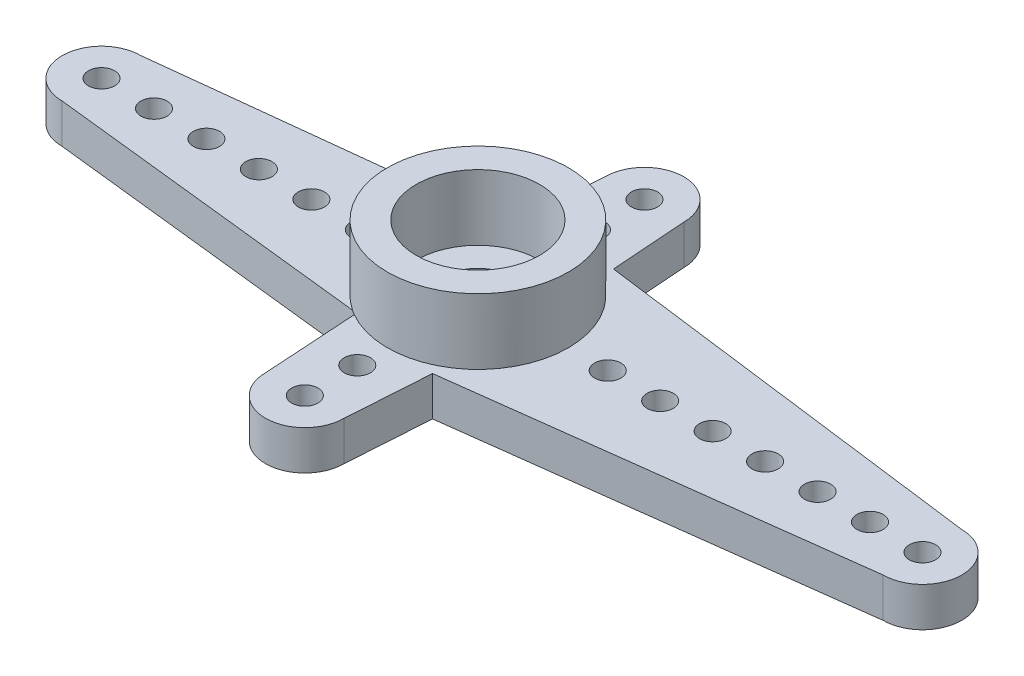
SolidWorks part; units mm, degrees
ref_plane "Front Plane" through (0, 0, 0) normal (0, 0, 1) x (1, 0, 0)
ref_plane "Top Plane" through (0, 0, 0) normal (0, 1, 0) x (1, 0, 0)
ref_plane "Right Plane" through (0, 0, 0) normal (1, 0, 0) x (0, 0, -1)
sketch "Sketch1" plane through (0, 0, 0) normal (0, 1, 0) x (1, 0, 0)
  line L0 (16.95, 0) -> (-14.35, 0) construction
  line L2 (16.95, 1.5) -> (1.7085, 3.4623)
  line L3 (1.7085, 3.4623) -> (1.7085, -3.4377) construction
  line L4 (1.7085, -3.4377) -> (16.95, -1.5)
  line L5 (-14.35, 1.5) -> (-1.7335, 2.9093)
  line L6 (-1.7335, 2.9093) -> (-1.7335, -2.8907) construction
  line L7 (-14.35, -1.5) -> (-1.7335, -2.8907)
  line L8 (0, 0) -> (0, 6.35) construction
  line L10 (1.5, 6.35) -> (1.7085, 3.4623)
  line L11 (-1.5, 6.35) -> (-1.7335, 2.9093)
  line L12 (0, 0) -> (0, -6.6) construction
  line L14 (-1.7335, -2.8907) -> (-1.5, -6.6)
  line L15 (1.5, -6.6) -> (1.7085, -3.4377)
  circle A0 centre (0, 0) radius 3.45 construction
  circle A1 centre (0, 0) radius 1.275
  circle A2 centre (0, 0) radius 2.35
  circle A3 centre (16.95, 0) radius 0.5
  circle A4 centre (12.95, 0) radius 0.5
  circle A5 centre (14.95, 0) radius 0.5
  circle A6 centre (10.95, 0) radius 0.5
  circle A7 centre (8.95, 0) radius 0.5
  circle A9 centre (6.95, 0) radius 0.5
  circle A10 centre (4.95, 0) radius 0.5
  circle A11 centre (-14.35, 0) radius 0.5
  circle A12 centre (-12.35, 0) radius 0.5
  circle A13 centre (-10.35, 0) radius 0.5
  circle A14 centre (-8.35, 0) radius 0.5
  circle A15 centre (-6.35, 0) radius 0.5
  circle A16 centre (-4.35, 0) radius 0.5
  arc A17 (-14.35, 1.5) -> (-14.35, -1.5) centre (-14.35, 0) ccw
  arc A18 (16.95, -1.5) -> (16.95, 1.5) centre (16.95, 0) ccw
  arc A19 (1.5, 6.35) -> (-1.5, 6.35) centre (0, 6.35) ccw
  circle A20 centre (0, 6.35) radius 0.5
  circle A21 centre (0, 4.35) radius 0.5
  arc A22 (-1.5, -6.6) -> (1.5, -6.6) centre (0, -6.6) ccw
  circle A23 centre (0, -6.6) radius 0.5
  circle A24 centre (0, -4.6) radius 0.5
  point P51 (0, 0)
  point P52 (0, 0)
  dimension "D1" = 16.95
  dimension "D2" = 2
  dimension "D3" = 2.55
  dimension "D4" = 4.7
  dimension "D5" = 6.9
  dimension "D6" = 1.5
  dimension "D7" = 14.35
  dimension "D8" = 6.6
  dimension "D9" = 6.35
sketch3d "3DSketch2" plane through (0, 0, 0) normal (0, 0, 1) x (1, 0, 0)
  dimension "D1" = 1.5
sketch "Sketch6" plane through (0, 1.5, 0) normal (0, 1, 0) x (1, 0, 0)
  circle A0 centre (0, 0) radius 1.275
  circle A1 centre (0, 0) radius 2.35
  circle A2 centre (0, 0) radius 3.45
extrude "Boss-Extrude1" add sketch "Sketch1" along normal blind 1.5 contours L14 A22 L15 L4 A18 L2 L10 A19 L11 L5 A17 L7 A24 A23 A2 A3 A4 A5 A6 A7 A9 A10 A11 A12 A13 A14 A15 A16 A20 A21 region at (18.0717, 0, 0)
extrude "Boss-Extrude2" add sketch "Sketch6" against normal blind 0.5 contours A1 A0 region at (-2.2835, 1.5, 0)
extrude "Boss-Extrude3" add sketch "Sketch6<3>" along normal blind 2.5 contours A2 A1 region at (-3.3524, 1.5, 0)
sketch "Sketch6<3>" plane through (0, 1.5, 0) normal (0, 1, 0) x (1, 0, 0) same geometry as "Sketch6"
